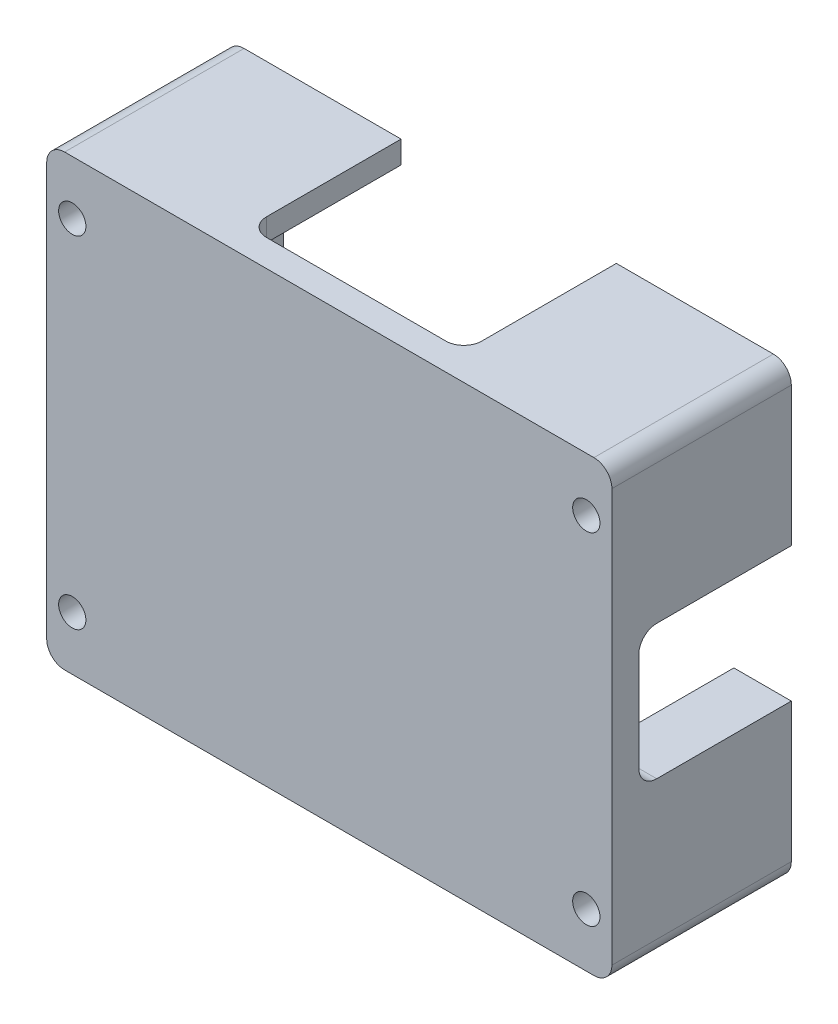
SolidWorks part; units mm, degrees
ref_plane "Front Plane" through (0, 0, 0) normal (0, 0, 1) x (1, 0, 0)
ref_plane "Top Plane" through (0, 0, 0) normal (0, 1, 0) x (1, 0, 0)
ref_plane "Right Plane" through (0, 0, 0) normal (1, 0, 0) x (0, 0, -1)
sketch "Sketch1" plane through (0, 0, 0) normal (0, 0, 1) x (1, 0, 0)
  line L1 (-40.005, 31.75) -> (40.005, 31.75)
  line L2 (-40.005, 31.75) -> (-40.005, -31.75)
  line L3 (-40.005, -31.75) -> (40.005, -31.75)
  line L4 (40.005, 31.75) -> (40.005, -31.75)
  dimension "D1" = 63.5
  dimension "D2" = 80.01
  dimension "D3" = 31.75
  dimension "D4" = 40.005
extrude "Boss-Extrude1" add sketch "Sketch1" along normal blind 25.4
sketch "Sketch2" plane through (0, 0, 0) normal (0, 0, 1) x (1, 0, 0)
  line L1 (31.877, 28.575) -> (-31.877, 28.575)
  line L2 (31.877, 28.575) -> (31.877, -28.575)
  line L3 (31.877, -28.575) -> (-31.877, -28.575)
  line L4 (-31.877, 28.575) -> (-31.877, -28.575)
  line L5 (40.005, -31.75) -> (40.005, 31.75) construction
  line L6 (-40.005, 31.75) -> (-40.005, -31.75) construction
  dimension "D1" = 8.128
  dimension "D2" = 28.575
  dimension "D3" = 57.15
  dimension "D4" = 8.128
extrude "Cut-Extrude1" cut sketch "Sketch2" along normal blind 22.86
sketch "Sketch3" plane through (0, 0, 0) normal (0, 1, 0) x (1, 0, 0)
  line L5 (-40.005, -25.4) -> (-40.005, 0) construction
  line L6 (40.005, -25.4) -> (40.005, 0) construction
  line L7 (-40.005, -12.7) -> (40.005, -12.7) construction
  line L8 (31.877, -5.08) -> (31.877, 0)
  line L9 (-31.877, 0) -> (31.877, 0)
  line L10 (-31.877, -5.08) -> (-31.877, 0)
  line L11 (-31.877, -5.08) -> (31.877, -5.08)
  line L12 (-34.925, 0) -> (34.925, 0) construction
  dimension "D1" = 5.08
  dimension "D2" = 8.128
  dimension "D3" = 8.128
sketch "Sketch6" plane through (0, 0, 0) normal (0, 0, 1) x (1, 0, 0)
  line L0 (0, 31.75) -> (0, -31.75) construction
  line L1 (40.005, 31.75) -> (-40.005, 31.75) construction
  line L2 (-40.005, -31.75) -> (40.005, -31.75) construction
  line L3 (13.97, 0) -> (-13.97, 0) construction
  line L4 (0, -13.97) -> (0, 13.97) construction
  point P6 (0, 24.13)
  point P10 (0, -24.13)
  point P14 (0, -24.13)
  point P15 (0, 24.13)
  dimension "D1" = 7.62
hole_wizard "#8 Clearance Hole1" positions "Sketch7" profile "Sketch8" hole size "#8" standard "ANSI Inch" end condition through all
sketch "Sketch7" plane through (0, 0, 0) normal (0, 0, -1) x (-1, 0, 0)
  line L1 (-36.3855, 24.13) -> (36.3855, 24.13)
  line L2 (-36.3855, 24.13) -> (-36.3855, -24.13)
  line L3 (-36.3855, -24.13) -> (36.3855, -24.13)
  line L4 (36.3855, 24.13) -> (36.3855, -24.13)
  line L5 (-36.3855, 24.13) -> (36.3855, -24.13) construction
  point P70 (0, 0)
  point P76 (-36.3855, 24.13)
  point P79 (36.3855, 24.13)
  point P82 (36.3855, -24.13)
  point P90 (-36.3855, -24.13)
  point P92 (0, 0)
  dimension "D1" = 72.771
  dimension "D2" = 48.26
sketch "Sketch8" plane through (36.3855, -24.13, 0) normal (1, 0, 0) x (0, 1, 0)
  line L0 (0, 0) -> (0, 25.4)
  line L1 (0, 25.4) -> (1.9304, 25.4)
  line L2 (1.9304, 25.4) -> (1.9304, 0)
  line L5 (1.9304, 0) -> (0, 0)
  line L11 (0, -6.35) -> (0, 107.95) construction
  dimension "Thru Hole Dia." = 3.8608
  dimension "Thru Hole Depth" = 25.4
sketch "Sketch11" plane through (0, 0, 0) normal (0, 0, 1) x (1, 0, 0)
  line L0 (0, -13.97) -> (0, 13.97) construction
  line L1 (-40.005, -31.75) -> (40.005, -31.75) construction
  point P0 (0, -21.59)
  dimension "D1" = 10.16
sketch "Sketch13" plane through (0, 0, 0) normal (0, 1, 0) x (1, 0, 0)
  line L1 (0, -13.97) -> (0, 13.97) construction
  line L2 (-10.16, 0) -> (-10.16, -21.59)
  line L3 (-10.16, -21.59) -> (10.16, -21.59)
  line L4 (10.16, -21.59) -> (10.16, 0)
  line L6 (-10.16, 0) -> (10.16, 0)
  line L10 (-31.877, 0) -> (31.877, 0) construction
  point P1 (-10.16, -21.59)
  point P4 (10.16, -21.59)
  dimension "D1" = 21.59
  dimension "D3" = 10.16
  dimension "D4" = 10.16
extrude "Cut-Extrude3" cut sketch "Sketch13" against normal blind 50.8
sketch "Sketch14" plane through (0, 0, 0) normal (0, 0, -1) x (-1, 0, 0)
  line L0 (-40.005, -31.75) -> (-40.005, 31.75) construction
  line L1 (-40.005, 9.525) -> (-31.877, 9.525)
  line L2 (-40.005, 9.525) -> (-40.005, -9.525)
  line L3 (-40.005, -9.525) -> (-31.877, -9.525)
  line L4 (-31.877, 9.525) -> (-31.877, -9.525)
  line L5 (-31.877, -28.575) -> (-31.877, 28.575) construction
  line L6 (31.877, 0) -> (-31.877, 0) construction
  line L7 (0, 13.97) -> (0, -13.97) construction
  line L8 (31.877, 9.525) -> (31.877, -9.525)
  line L9 (40.005, -9.525) -> (31.877, -9.525)
  line L10 (40.005, 9.525) -> (40.005, -9.525)
  line L11 (40.005, 9.525) -> (31.877, 9.525)
  point P8 (-31.877, 0)
  dimension "D1" = 19.05
extrude "Cut-Extrude4" cut sketch "Sketch14" against normal blind 21.59
sketch "Sketch15" plane through (0, 0, 0) normal (0, 0, -1) x (-1, 0, 0)
  line L0 (-40.005, 31.75) -> (40.005, 31.75) construction
  line L1 (-15.24, 31.75) -> (15.24, 31.75)
  line L2 (-15.24, 31.75) -> (-15.24, 28.575)
  line L3 (-15.24, 28.575) -> (15.24, 28.575)
  line L4 (15.24, 31.75) -> (15.24, 28.575)
  line L5 (-31.877, 28.575) -> (31.877, 28.575) construction
  line L6 (0, 13.97) -> (0, -13.97) construction
  line L7 (13.97, 0) -> (-13.97, 0) construction
  line L8 (15.24, -31.75) -> (15.24, -28.575)
  line L9 (-15.24, -28.575) -> (15.24, -28.575)
  line L10 (-15.24, -31.75) -> (-15.24, -28.575)
  line L11 (-15.24, -31.75) -> (15.24, -31.75)
  point P8 (0, 28.575)
  dimension "D1" = 30.48
extrude "Cut-Extrude5" cut sketch "Sketch15" against normal blind 21.59
fillet "Fillet1" radius 2.54 2 edges at (31.877, 0, 22.86) (-31.877, 0, 22.86)
fillet "Fillet2" radius 2.54 8 edges at (-15.24, 30.1625, 21.59) (15.24, 30.1625, 21.59) (15.24, -30.1625, 21.59) (-15.24, -30.1625, 21.59) (-35.7709, 9.525, 21.59) (-35.7709, -9.525, 21.59) (35.7709, -9.525, 21.59) (35.7709, 9.525, 21.59)
fillet "Fillet3" radius 2.54 4 edges at (-40.005, 31.75, 12.7) (-40.005, -31.75, 12.7) (40.005, 31.75, 12.7) (40.005, -31.75, 12.7)
